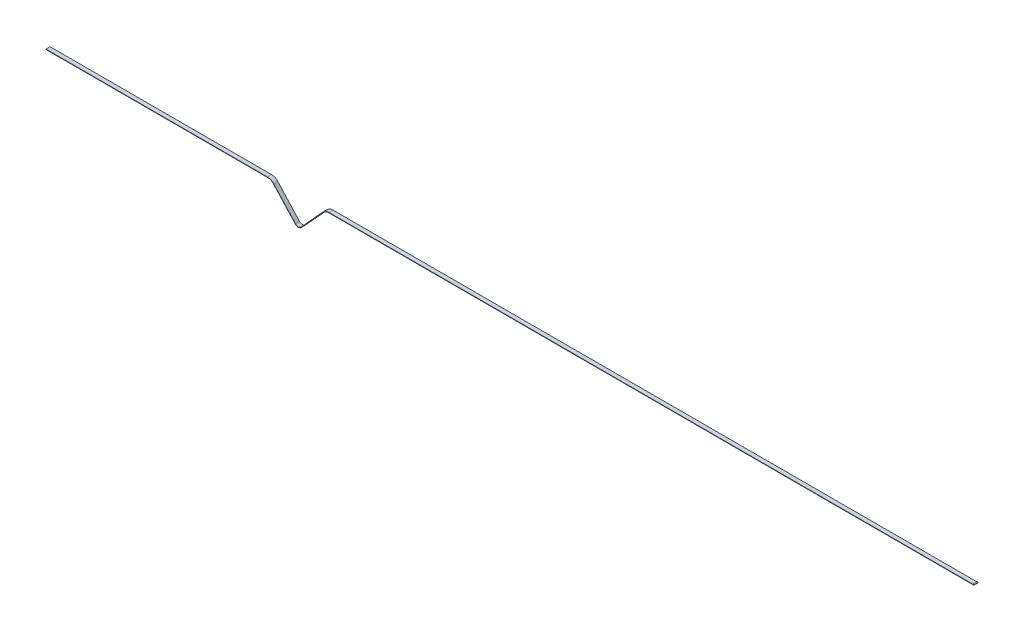
SolidWorks part; units mm, degrees
material "BUTYL"
ref_plane "Front Plane" through (0, 0, 0) normal (0, 0, 1) x (1, 0, 0)
ref_plane "Top Plane" through (0, 0, 0) normal (0, 1, 0) x (1, 0, 0)
ref_plane "Right Plane" through (0, 0, 0) normal (1, 0, 0) x (0, 0, -1)
sketch "Sketch1" plane through (0, 0, 0) normal (1, 0, 0) x (0, 0, -1)
  line L1 (0, 0) -> (6, 0)
  line L2 (0, 0) -> (0, 0.63)
  line L3 (0, 0.63) -> (6, 0.63)
  line L4 (6, 0) -> (6, 0.63)
  dimension "D1" = 0.63
  dimension "D2" = 6
sketch "Sketch2" plane through (0, 0, 0) normal (0, 0, 1) x (1, 0, 0)
  line L0 (0, 0) -> (-953.1696, 0)
  line L1 (-961.9886, -3.886) -> (-994.2304, -39.1468)
  line L2 (-1003.2487, -39.1468) -> (-1035.4905, -3.886)
  line L3 (-1044.3096, 0) -> (-1371.6, 0)
  arc A0 (-953.1696, 0) -> (-961.9886, -3.886) centre (-953.1696, -11.95) ccw
  arc A1 (-994.2304, -39.1468) -> (-1003.2487, -39.1468) centre (-998.7396, -35.0237) cw
  arc A2 (-1035.4905, -3.886) -> (-1044.3096, 0) centre (-1044.3096, -11.95) ccw
  circle A3 centre (-953.1696, -11.95) radius 11.95 construction
  circle A4 centre (-1044.3096, -11.95) radius 11.95 construction
  circle A5 centre (-998.7396, -35.0237) radius 6.11 construction
  dimension "D1" = 6.11
  dimension "D4" = 1371.6
sweep "Sweep1" add profiles "Sketch1" path "Sketch2"
sketch "Sketch3" plane through (0, 0, 0) normal (0, 0, 1) x (1, 0, 0)
  line L0 (0, 0.63) -> (-953.1696, 0.63) construction
  line L1 (-1.5, 0.63) -> (-1.5, 0)
  line L2 (0, 0) -> (-953.1696, 0) construction
  line L3 (-1.5, 0) -> (0, 0)
  line L4 (0, 0) -> (0, 0.63)
  arc A1 (0, 0.63) -> (-1.5, 0.63) centre (-0.75, 0.63) ccw
  dimension "D1" = 0.75
extrude "Boss-Extrude1" add sketch "Sketch3" against normal through all
pattern_curve "CrvPattern1" [suppressed] of bodies 102 driven by "Sketch2" parameters "D1"=2000, "D3"=2, "D2"=1, "D4"=10
